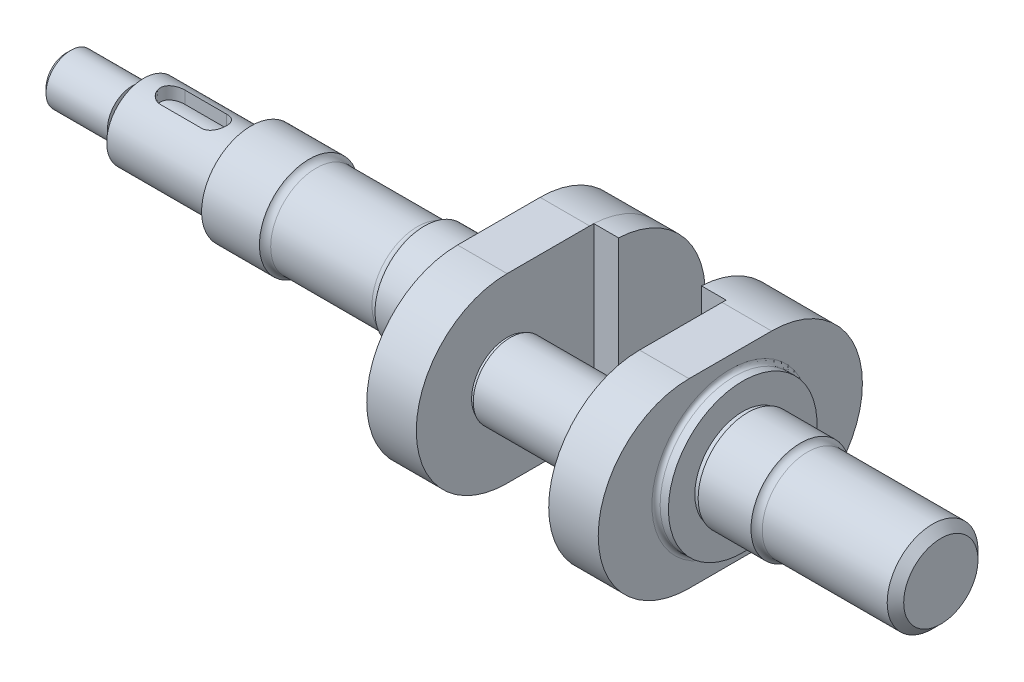
SolidWorks part; units mm, degrees
ref_plane "Piano frontale" through (0, 0, 0) normal (0, 0, 1) x (1, 0, 0)
ref_plane "Piano superiore" through (0, 0, 0) normal (0, 1, 0) x (1, 0, 0)
ref_plane "Piano destro" through (0, 0, 0) normal (1, 0, 0) x (0, 0, -1)
sketch "Schizzo1" plane through (0, 0, 0) normal (1, 0, 0) x (0, 0, -1)
  line L0 (-5, 0) -> (5, 0) construction
  line L1 (-5, 11) -> (5, 11)
  line L2 (-5, -11) -> (5, -11)
  arc A0 (-5, 11) -> (-5, -11) centre (-5, 0) ccw
  arc A1 (5, -11) -> (5, 11) centre (5, 0) ccw
  point P3 (0, 0)
  dimension "D2" = 11
  dimension "D1" = 10
extrude "Estrusione-Estrusione1" add sketch "Schizzo1" along normal blind 6
sketch "Schizzo3" plane through (0, 0, 0) normal (0, 1, 0) x (1, 0, 0)
  line L1 (0, 0) -> (-2, 0)
  line L2 (0, 0) -> (0, -9)
  line L3 (0, -9) -> (-2, -9)
  line L4 (-2, 0) -> (-2, -9)
  line L5 (-2, 0) -> (-2.6, 0)
  line L6 (-2, 0) -> (-2, -5.8)
  line L7 (-2, -5.8) -> (-2.6, -5.8)
  line L8 (-2.6, 0) -> (-2.6, -5.8)
  line L9 (-2.6, 0) -> (-9, 0)
  line L10 (-2.6, 0) -> (-2.6, -6)
  line L11 (-2.6, -6) -> (-9, -6)
  line L12 (-9, 0) -> (-9, -6)
  line L13 (-9, 0) -> (-23, 0)
  line L14 (-9, 0) -> (-9, -5.5)
  line L15 (-9, -5.5) -> (-23, -5.5)
  line L16 (-23, 0) -> (-23, -5.5)
  line L17 (-23, 0) -> (-30, 0)
  line L18 (-23, 0) -> (-23, -6)
  line L19 (-23, -6) -> (-30, -6)
  line L20 (-30, 0) -> (-30, -6)
  line L21 (-30, 0) -> (-43, 0)
  line L22 (-30, 0) -> (-30, -4.5)
  line L23 (-30, -4.5) -> (-43, -4.5)
  line L24 (-43, 0) -> (-43, -4.5)
  line L25 (-43, 0) -> (-44.4, 0)
  line L26 (-43, 0) -> (-43, -2.2)
  line L27 (-43, -2.2) -> (-44.4, -2.2)
  line L28 (-44.4, 0) -> (-44.4, -2.2)
  line L29 (-44.4, 0) -> (-52.4, 0)
  line L30 (-44.4, 0) -> (-44.4, -3)
  line L31 (-44.4, -3) -> (-52.4, -3)
  line L32 (-52.4, 0) -> (-52.4, -3)
  dimension "D1" = 2
  dimension "D2" = 52.4
  dimension "D3" = 30
  dimension "D4" = 23
  dimension "D5" = 9
  dimension "D6" = 0.6
  dimension "D7" = 43
  dimension "D8" = 1.4
  dimension "D9" = 3
  dimension "D10" = 4.5
  dimension "D11" = 2.2
  dimension "D12" = 6
  dimension "D13" = 5.5
  dimension "D14" = 6
  dimension "D15" = 9
  dimension "D16" = 5.8
revolve "Rivoluzione1" add sketch "Schizzo3" angle 360 about L13
chamfer "Smusso1" distance 0.55 angle 45 1 edges at (-52.4, 0, -3)
fillet "Raccordo1" radius 0.5 2 edges at (-30, 0, -4.5) (0, 0, -9)
fillet "Raccordo2" radius 1 2 edges at (-9, 0, -5.5) (-23, 0, -5.5)
sketch "Schizzo4" plane through (6, 0, 0) normal (1, 0, 0) x (0, 0, -1)
  line L1 (5, 11) -> (-5, 11) construction
  line L2 (5.5, 11) -> (5.5, -11)
  line L3 (-5, -11) -> (5, -11) construction
  arc A1 (5.5, 11) -> (5.5, -11) centre (4.9881, 0) cw
  dimension "D1" = 5.5
extrude "Estrusione-Estrusione2" add sketch "Schizzo4" along normal blind 3
sketch "Schizzo5" plane through (0, 0, 0) normal (0, 1, 0) x (1, 0, 0)
  line L1 (6.4, -5) -> (21.64, -5)
  line L2 (6.4, -5) -> (6.4, -9.5)
  line L3 (6.4, -9.5) -> (21.64, -9.5)
  line L4 (21.64, -5) -> (21.64, -9.5)
  line L7 (21.64, -5) -> (21.64, -8)
  line L14 (0, 9.5) -> (0, -9.5) construction
  line L15 (21.64, -5) -> (22.04, -5)
  line L16 (6, -5) -> (6.4, -5)
  line L17 (6, -5) -> (6, -9.3)
  line L18 (6, -9.3) -> (6.4, -9.3)
  line L19 (6.4, -5) -> (6.4, -9.3)
  line L20 (21.64, -5) -> (21.64, -9.3)
  line L21 (21.64, -9.3) -> (22.04, -9.3)
  line L22 (22.04, -5) -> (22.04, -9.3)
  point P10 (21.84, -9.3)
  dimension "D1" = 5
  dimension "D2" = 4.5
  dimension "D3" = 4.3
  dimension "D4" = 0.4
  dimension "D5" = 21.64
  dimension "D8" = 0.4
  dimension "D9" = 4.3
revolve "Rivoluzione2" add sketch "Schizzo5" angle 360 about L1
sketch "Schizzo7" plane through (0, 0, 0) normal (0, 1, 0) x (1, 0, 0)
  line L0 (-39.5, 0) -> (-34.5, 0) construction
  line L1 (-39.5, 1.5) -> (-34.5, 1.5)
  line L2 (-39.5, -1.5) -> (-34.5, -1.5)
  line L3 (-30, 5) -> (-30, -5) construction
  arc A0 (-39.5, 1.5) -> (-39.5, -1.5) centre (-39.5, 0) ccw
  arc A1 (-34.5, -1.5) -> (-34.5, 1.5) centre (-34.5, 0) ccw
  point P2 (-37, 0)
  dimension "D4" = 1.5
  dimension "D1" = 37
  dimension "D2" = 7
  dimension "D3" = 5
extrude "Taglio-Estrusione1" cut sketch "Schizzo7" against normal blind 1.5 from surface starting at face at (-30.5, 0, -4.5)
sketch "Schizzo8" plane through (22.04, 0, 0) normal (1, 0, 0) x (0, 0, -1)
  line L0 (-5, 0) -> (5, 0) construction
  line L4 (-5, 11) -> (5, 11)
  line L5 (-5, -11) -> (5, -11)
  arc A2 (-5, 11) -> (-5, -11) centre (-5, 0) ccw
  arc A3 (5, -11) -> (5, 11) centre (5, 0) ccw
  point P3 (0, 0)
  dimension "D2" = 11
  dimension "D1" = 10
extrude "Estrusione-Estrusione3" add sketch "Schizzo8" along normal blind 6
sketch "Schizzo9" plane through (22.04, 0, 0) normal (-1, 0, 0) x (0, 0, 1)
  line L0 (-5.5, 10.9886) -> (-5.5, -10.9886)
  arc A0 (-5, 11) -> (-5, -11) centre (-5, 0) ccw construction
  arc A1 (-5.5, 10.9886) -> (-5.5, -10.9886) centre (-5, 0) ccw
  dimension "D1" = 5.5
extrude "Estrusione-Estrusione4" add sketch "Schizzo9" along normal blind 3
sketch "Schizzo11" plane through (0, 0, 0) normal (0, 1, 0) x (1, 0, 0)
  line L0 (28.04, 5) -> (28.04, -5) construction
  line L1 (28.04, 0) -> (29.54, 0)
  line L2 (28.04, 0) -> (28.04, -9)
  line L3 (28.04, -9) -> (29.54, -9)
  line L4 (29.54, 0) -> (29.54, -9)
  line L5 (-2, -9) -> (-0.5, -9) construction
  line L6 (29.54, 0) -> (30.14, 0)
  line L7 (29.54, 0) -> (29.54, -5.8)
  line L8 (29.54, -5.8) -> (30.14, -5.8)
  line L9 (30.14, 0) -> (30.14, -5.8)
  line L10 (30.14, 0) -> (36.54, 0)
  line L11 (30.14, 0) -> (30.14, -6)
  line L12 (30.14, -6) -> (36.54, -6)
  line L13 (36.54, 0) -> (36.54, -6)
  line L14 (-2.6, -5.8) -> (-2, -5.8) construction
  line L17 (-9, -6) -> (-2.6, -6) construction
  line L19 (36.54, 0) -> (53.54, 0)
  line L20 (36.54, 0) -> (36.54, -5.5)
  line L21 (36.54, -5.5) -> (53.54, -5.5)
  line L22 (53.54, 0) -> (53.54, -5.5)
  line L23 (-22.134, -5.5) -> (-9.866, -5.5) construction
  point P23 (-89.0109, 4.9052)
  dimension "D1" = 17
revolve "Rivoluzione3" add sketch "Schizzo11" angle 360 about L10
chamfer "Smusso3" distance 1 angle 45 1 edges at (53.54, 0, 5.5)
fillet "Raccordo3" radius 0.5 1 edges at (28.04, 0, 9)
fillet "Raccordo4" radius 1 1 edges at (36.54, 0, 5.5)
